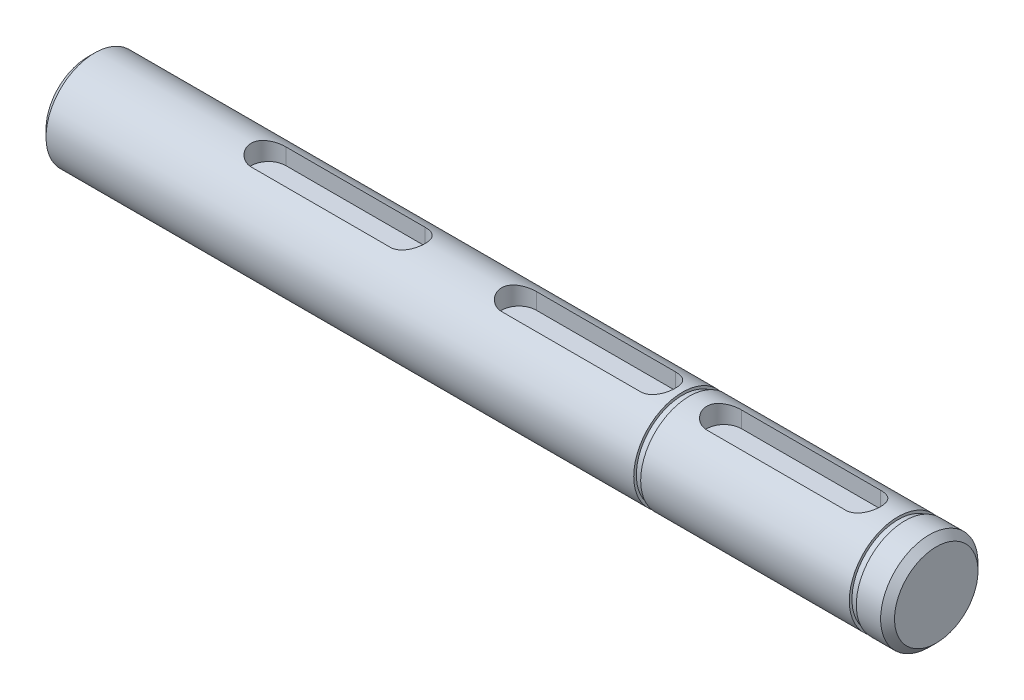
SolidWorks part; units mm, degrees
ref_plane "Front Plane" through (0, 0, 0) normal (0, 0, 1) x (1, 0, 0)
ref_plane "Top Plane" through (0, 0, 0) normal (0, 1, 0) x (1, 0, 0)
ref_plane "Right Plane" through (0, 0, 0) normal (1, 0, 0) x (0, 0, -1)
sketch "Sketch1" plane through (0, 0, 0) normal (1, 0, 0) x (0, 0, -1)
  circle A0 centre (0, 0) radius 7
  dimension "D1" = 14
extrude "Boss-Extrude1" add sketch "Sketch1" along normal mid plane 68
ref_plane "Plane1" through (0, 7, 0) normal (0, 1, 0) x (1, 0, 0)
sketch "Sketch4" plane through (0, 7, 0) normal (0, 1, 0) x (1, 0, 0)
  line L0 (-28, 0) -> (-8, 0) construction
  line L1 (-28, 2.5) -> (-8, 2.5)
  line L2 (-28, -2.5) -> (-8, -2.5)
  arc A0 (-28, 2.5) -> (-28, -2.5) centre (-28, 0) ccw
  arc A1 (-8, -2.5) -> (-8, 2.5) centre (-8, 0) ccw
  point P3 (-18, 0)
  dimension "D2" = 2.5
  dimension "D1" = 20
  dimension "D3" = 8
extrude "Cut-Extrude1" cut sketch "Sketch4" against normal blind 2.8
mirror "Mirror1" about plane through (0, 0, 0) normal (1, 0, 0) of "Cut-Extrude1"
sketch "Sketch5" plane through (-34, 0, 0) normal (-1, 0, 0) x (0, 0, 1)
  circle A1 centre (0, 0) radius 7
  circle A2 centre (0, 0) radius 7
  dimension "D1" = 0
extrude "Boss-Extrude3" add sketch "Sketch5" along normal blind 20
sketch "Sketch6" plane through (0, 0, 0) normal (0, 1, 0) x (1, 0, 0)
  line L0 (-54, 7) -> (-54, -7) construction
  line L1 (-46.5, 0) -> (-54, 0) construction
  circle A0 centre (-46.5, 0) radius 2.5
  dimension "D1" = 5
  dimension "D2" = 7.5
sketch "Sketch7" plane through (34, 0, 0) normal (1, 0, 0) x (0, 0, -1)
  circle A2 centre (0, 0) radius 7
  dimension "D1" = 14
extrude "Boss-Extrude4" add sketch "Sketch7" along normal blind 34
ref_plane "Plane2" through (0, 0, 7) normal (0, 0, 1) x (1, 0, 0)
sketch "Sketch11" plane through (0, 0, 0) normal (0, 0, 1) x (1, 0, 0)
  line L0 (68, 7) -> (30.5, 7) construction
  line L1 (63.5, 6.625) -> (62.5, 6.625)
  line L2 (63.5, 6.625) -> (63.5, 7.375)
  line L3 (63.5, 7.375) -> (62.5, 7.375)
  line L4 (62.5, 6.625) -> (62.5, 7.375)
  line L5 (63.5, 6.625) -> (62.5, 7.375) construction
  line L6 (63.5, 7.375) -> (62.5, 6.625) construction
  line L7 (68, 7) -> (30.5, 7) construction
  line L8 (32.5, 6.625) -> (31.5, 6.625)
  line L9 (32.5, 6.625) -> (32.5, 7.375)
  line L10 (32.5, 7.375) -> (31.5, 7.375)
  line L11 (31.5, 6.625) -> (31.5, 7.375)
  line L12 (32.5, 6.625) -> (31.5, 7.375) construction
  line L13 (32.5, 7.375) -> (31.5, 6.625) construction
  line L14 (68, -7) -> (68, 7) construction
  point P0 (63, 7)
  point P7 (32, 7)
  dimension "D1" = 1
  dimension "D2" = 0.75
  dimension "D3" = 30
  dimension "D4" = 4.5
ref_axis "Axis1" through (71.5, 0, 0) along (-1, 0, 0)
revolve "Cut-Revolve1" cut sketch "Sketch11" angle 360 about axis through (71.5, 0, 0) along (-1, 0, 0)
chamfer "Chamfer1" distance 1 angle 45 2 edges at (-54, 0, 7) (68, 0, -7)
sketch "Sketch9" plane through (0, 7, 0) normal (0, 1, 0) x (1, 0, 0)
  line L0 (37.5, 0) -> (57.5, 0) construction
  line L1 (37.5, 2.5) -> (57.5, 2.5)
  line L2 (37.5, -2.5) -> (57.5, -2.5)
  line L3 (37.5, 0) -> (32.5, 0) construction
  line L5 (32.5, 7) -> (32.5, -7) construction
  line L6 (57.5, 0) -> (62.5, 0) construction
  line L7 (62.5, -6.625) -> (62.5, 6.625) construction
  arc A0 (37.5, 2.5) -> (37.5, -2.5) centre (37.5, 0) ccw
  arc A1 (57.5, -2.5) -> (57.5, 2.5) centre (57.5, 0) ccw
  point P3 (47.5, 0)
  dimension "D1" = 2.5
  dimension "D2" = 20
extrude "Cut-Extrude3" cut sketch "Sketch9" against normal blind 2.8
